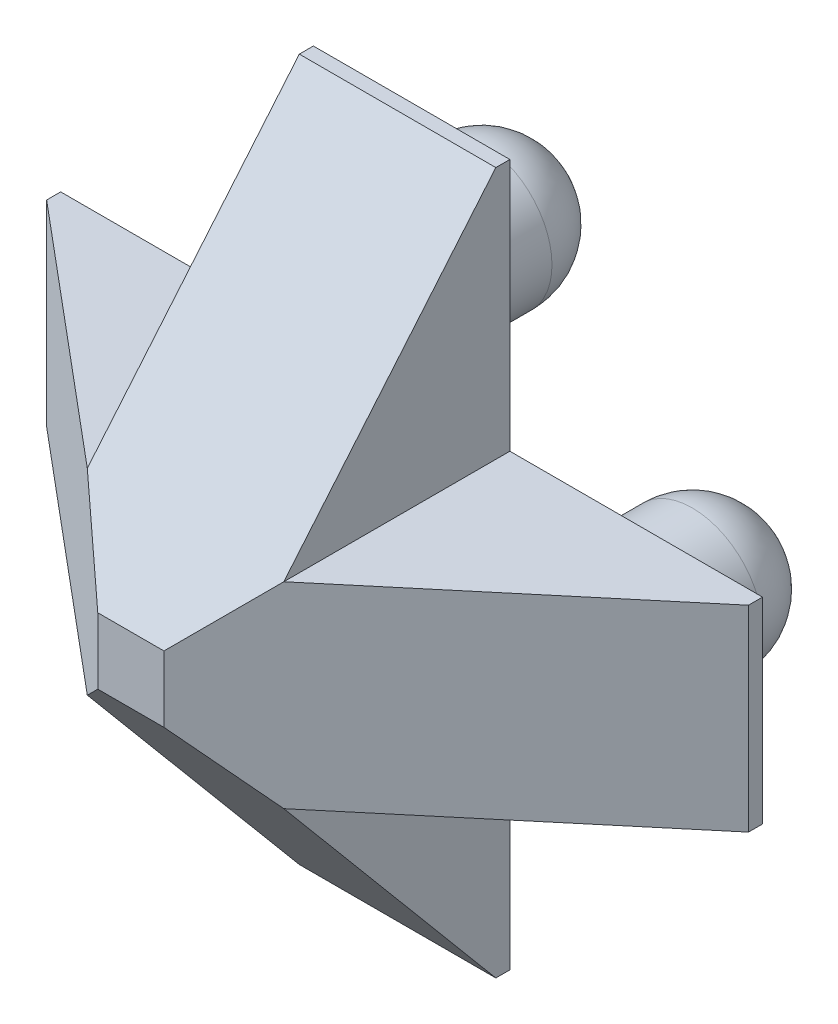
SolidWorks part; units mm, degrees
ref_plane "Front Plane" through (0, 0, 0) normal (0, 0, 1) x (1, 0, 0)
ref_plane "Top Plane" through (0, 0, 0) normal (0, 1, 0) x (1, 0, 0)
ref_plane "Right Plane" through (0, 0, 0) normal (1, 0, 0) x (0, 0, -1)
sketch "Sketch1" plane through (0, 0, 0) normal (0, 0, 1) x (1, 0, 0)
  line L1 (22.86, 0) -> (40.64, 0)
  line L2 (0, 22.86) -> (0, 40.64)
  line L3 (22.86, 63.5) -> (40.64, 63.5)
  line L4 (63.5, 22.86) -> (63.5, 40.64)
  line L7 (0, 40.64) -> (22.86, 40.64)
  line L8 (22.86, 63.5) -> (22.86, 40.64)
  line L11 (0, 22.86) -> (22.86, 22.86)
  line L12 (22.86, 0) -> (22.86, 22.86)
  line L15 (63.5, 40.64) -> (40.64, 40.64)
  line L16 (40.64, 63.5) -> (40.64, 40.64)
  line L19 (63.5, 22.86) -> (40.64, 22.86)
  line L20 (40.64, 0) -> (40.64, 22.86)
  dimension "D1" = 63.5
  dimension "D2" = 63.5
  dimension "D3" = 22.86
  dimension "D4" = 63.5
  dimension "D5" = 63.5
extrude "Boss-Extrude1" add sketch "Sketch1" along normal blind 25.4
chamfer "Chamfer1" distance 24.13 angle 50 4 edges at (31.75, 0, 25.4) (63.5, 31.75, 25.4) (0, 31.75, 25.4) (31.75, 63.5, 25.4) first distance on face at (31.75, 0, 12.7) first distance on face at (63.5, 31.75, 12.7) first distance on face at (0, 31.75, 12.7) first distance on face at (31.75, 63.5, 12.7)
sketch "Sketch2" plane through (0, 0, 0) normal (0, 0, -1) x (-1, 0, 0)
  line L0 (-31.75, 0) -> (-31.75, 63.5) construction
  line L1 (-22.86, 0) -> (-40.64, 0) construction
  line L2 (-40.64, 63.5) -> (-22.86, 63.5) construction
  line L3 (-63.5, 31.75) -> (0, 31.75) construction
  line L4 (-63.5, 22.86) -> (-63.5, 40.64) construction
  line L5 (0, 40.64) -> (0, 22.86) construction
  circle A0 centre (-31.75, 12.7) radius 6.35
  circle A1 centre (-50.8, 31.75) radius 6.35
  circle A2 centre (-31.75, 50.8) radius 6.35
  circle A3 centre (-12.7, 31.75) radius 6.35
  point P14 (-31.75, 31.75)
  dimension "D2" = 12.7
  dimension "D4" = 12.7
  dimension "D5" = 12.7
  dimension "D7" = 12.7
  dimension "D1" = 19.05
  dimension "D3" = 19.05
  dimension "D6" = 19.05
  dimension "D8" = 19.05
extrude "Boss-Extrude2" add sketch "Sketch2" along normal blind 12.7 contours A1 | A3 | A0 | A2 region at (31.75, 12.7, 0) region at (50.8, 31.75, 0) region at (12.7, 31.75, 0)
fillet "Fillet1" radius 6.35 4 edges at (44.45, 31.75, -12.7) (25.4, 12.7, -12.7) (25.4, 50.8, -12.7) (6.35, 31.75, -12.7)
